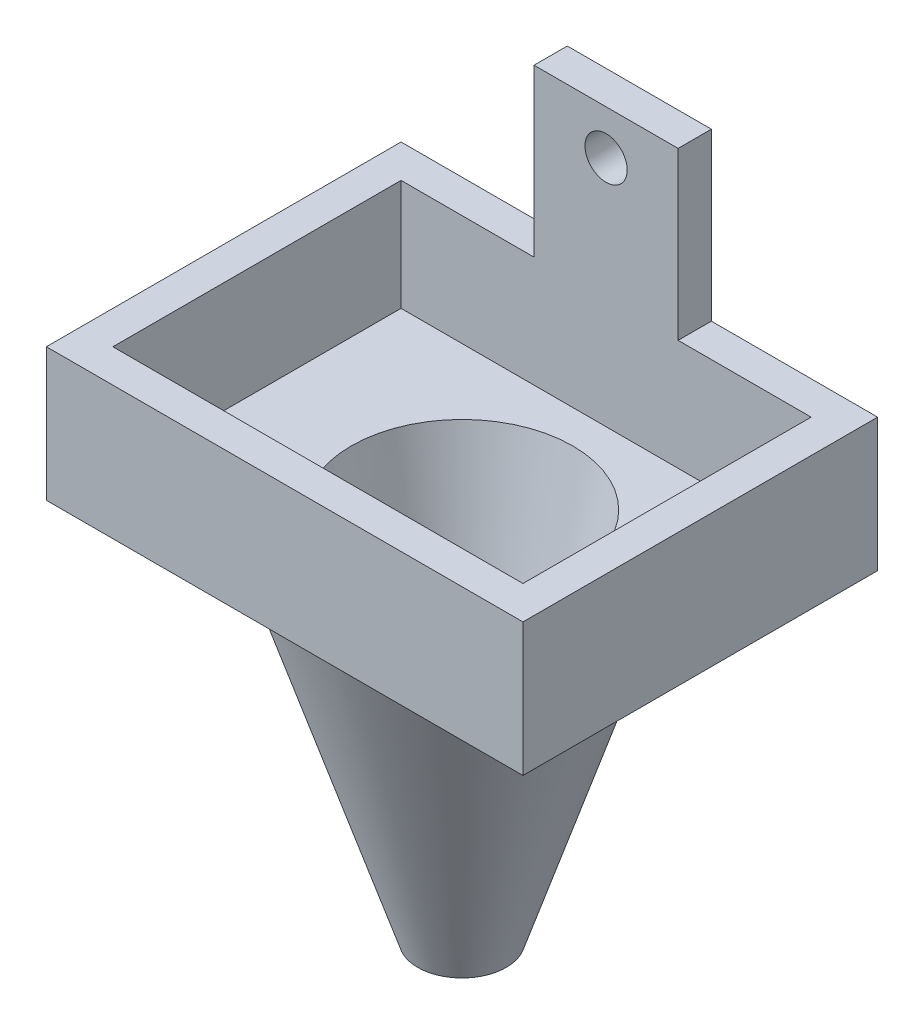
SolidWorks part; units mm, degrees
ref_plane "Front Plane" through (0, 0, 0) normal (0, 0, 1) x (1, 0, 0)
ref_plane "Top Plane" through (0, 0, 0) normal (0, 1, 0) x (1, 0, 0)
ref_plane "Right Plane" through (0, 0, 0) normal (1, 0, 0) x (0, 0, -1)
sketch "Sketch1" plane through (0, 0, 0) normal (0, 1, 0) x (1, 0, 0)
  line L1 (0, 0) -> (37, 0)
  line L2 (0, 0) -> (0, 26)
  line L3 (0, 26) -> (37, 26)
  line L4 (37, 0) -> (37, 26)
  line L5 (-3, -3) -> (40, -3)
  line L6 (-3, -3) -> (-3, 29)
  line L7 (-3, 29) -> (40, 29)
  line L8 (40, -3) -> (40, 29)
  dimension "D1" = 26
  dimension "D2" = 37
  dimension "D3" = 3
  dimension "D4" = 3
  dimension "D5" = 3
  dimension "D6" = 3
extrude "Boss-Extrude1" add sketch "Sketch1" along normal blind 10
sketch "Sketch2" plane through (0, 10, 0) normal (0, 1, 0) x (1, 0, 0)
  line L0 (37, 26) -> (0, 26) construction
  line L1 (25, 26) -> (12, 26)
  line L2 (25, 26) -> (25, 29)
  line L3 (25, 29) -> (12, 29)
  line L4 (12, 26) -> (12, 29)
  line L5 (40, -3) -> (40, 29) construction
  line L6 (-3, 29) -> (-3, -3) construction
  dimension "D1" = 3
  dimension "D2" = 15
  dimension "D3" = 15
extrude "Boss-Extrude2" add sketch "Sketch2" along normal blind 15
sketch "Sketch3" plane through (0, 0, -29) normal (0, 0, -1) x (-1, 0, 0)
  line L0 (-25, 25) -> (-12, 25) construction
  line L1 (-25, 25) -> (-25, 10) construction
  circle A0 centre (-18.5, 21) radius 1.905
  dimension "D1" = 3.81
  dimension "D2" = 4
  dimension "D3" = 6.5
extrude "Cut-Extrude1" cut sketch "Sketch3" against normal up to next
sketch "Sketch4" plane through (0, 0, 0) normal (0, -1, 0) x (1, 0, 0)
  line L1 (40, -29) -> (-3, -29)
  line L2 (40, -29) -> (40, 3)
  line L3 (40, 3) -> (-3, 3)
  line L4 (-3, -29) -> (-3, 3)
extrude "Boss-Extrude3" add sketch "Sketch4" along normal blind 2
sketch "Sketch5" plane through (0, -2, 0) normal (0, -1, 0) x (1, 0, 0)
  line L0 (-3, -29) -> (40, -29) construction
  line L2 (-3, 3) -> (-3, -29) construction
  circle A0 centre (18.5, -13) radius 10
  dimension "D1" = 16
  dimension "D2" = 21.5
extrude "Cut-Extrude2" cut sketch "Sketch5" against normal up to next
sketch "Sketch8" plane through (0, -2, 0) normal (0, -1, 0) x (1, 0, 0)
  line L0 (-3, -13) -> (40, -13) construction
  line L1 (-3, 3) -> (-3, -29) construction
  line L2 (40, -29) -> (40, 3) construction
  point P0 (18.5, -13)
ref_plane "Plane1" through (0, 0, -13) normal (0, 0, 1) x (1, 0, 0)
sketch "Sketch9" plane through (0, 0, -13) normal (0, 0, 1) x (1, 0, 0)
  line L0 (28.5, 0) -> (21.5, -33.75)
  line L1 (21.5, -33.75) -> (22.5, -33.75)
  line L2 (22.5, -33.75) -> (33.5, 0)
  line L3 (33.5, 0) -> (28.5, 0)
  line L4 (-3, -2) -> (40, -2) construction
  dimension "D1" = 1
  dimension "D2" = 3
  dimension "D3" = 31.75
  dimension "D4" = 5
ref_axis "Axis1" through (18.5, -2, -13) along (0, -1, 0)
revolve "Revolve1" add sketch "Sketch9" angle 360 about axis through (18.5, -2, -13) along (0, -1, 0)
sketch "Sketch11" plane through (-3, 0, 0) normal (-1, 0, 0) x (0, 0, 1)
  circle A0 centre (-16.2172, -43.6109) radius 3.175
ref_plane "Plane2" through (18.5, 0, 0) normal (-1, 0, 0) x (0, -1, 0)
sketch "Sketch12" plane through (18.5, 0, 0) normal (-1, 0, 0) x (0, -1, 0)
  line L0 (13.2219, -28.0503) -> (22.612, -20.6302) construction
  line L2 (2, -27.3481) -> (33.75, -17) construction
  line L3 (2, -27.3481) -> (33.75, -17) construction
ref_axis "Axis2" through (18.5, -13.2219, -28.0503) along (0, -0.7846, 0.62)
ref_plane "Plane3" through (18.5, -13.2219, -28.0503) normal (0, -0.7846, 0.62) x (-1, 0, 0)
sketch "Sketch14" plane through (18.5, -13.2219, -28.0503) normal (0, -0.7846, 0.62) x (-1, 0, 0)
  circle A0 centre (0.3057, 0) radius 2.75
  dimension "D1" = 5.5
extrude "Boss-Extrude4" add sketch "Sketch14" along normal blind 25 from offset 5 offset against normal yes
sketch "Sketch16" plane through (0, 9.4287, -7.4506) normal (0, 0.7846, -0.62) x (1, 0, 0)
  circle A0 centre (18.1943, 30.2059) radius 1.75
  circle A1 centre (18.1943, 30.2059) radius 2.75 construction
  dimension "D1" = 1
extrude "Cut-Extrude3" cut sketch "Sketch16" against normal blind 30
sketch "Sketch17" plane through (0, -33.75, 0) normal (0, -1, 0) x (1, 0, 0)
  circle A0 centre (18.5, -13) radius 2.5
  dimension "D1" = 5
extrude "Cut-Extrude4" cut sketch "Sketch17" against normal blind 10
